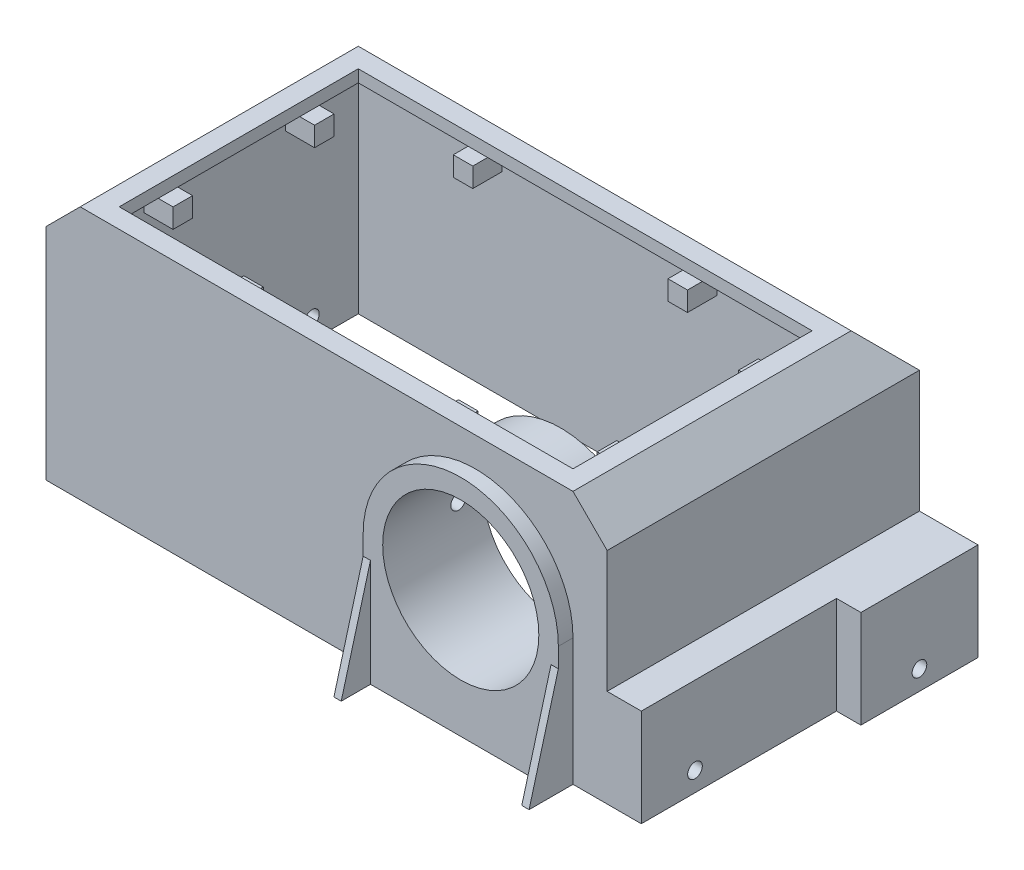
SolidWorks part; units mm, degrees
ref_plane "Front" through (0, 0, 0) normal (0, 0, 1) x (1, 0, 0)
ref_plane "Top" through (0, 0, 0) normal (0, 1, 0) x (1, 0, 0)
ref_plane "Right" through (0, 0, 0) normal (1, 0, 0) x (0, 0, -1)
sketch "Sketch1" plane through (0, 0, 0) normal (0, 0, 1) x (1, 0, 0)
  line L0 (63.5, -6) -> (51.5, -6)
  line L1 (-63.5, -26) -> (63.5, -26)
  line L2 (-63.5, -26) -> (-63.5, 26)
  line L3 (-63.5, 26) -> (63.5, 26)
  line L4 (63.5, -26) -> (63.5, 26)
  line L5 (-63.5, -26) -> (63.5, 26) construction
  line L6 (-63.5, 26) -> (63.5, -26) construction
  line L7 (51.5, -6) -> (51.5, 26)
  point P0 (0, 0)
  dimension "D1" = 52
  dimension "D2" = 127
  dimension "D3" = 12
  dimension "D4" = 20
extrude "Boss-Extrude1" add sketch "Sketch1" along normal blind 64 contours L0 L7 L3 L2 L1 L4 region at (-3.5498, -0.6174, 0)
sketch "Sketch2" plane through (0, 0, 64) normal (0, 0, 1) x (1, 0, 0)
  line L0 (-63.5, -26) -> (63.5, -26) construction
  line L1 (51.5, -6) -> (51.5, 26) construction
  circle A0 centre (24.5, 0) radius 16
  circle A1 centre (24.5, 0) radius 20
  dimension "D1" = 32
  dimension "D3" = 26
  dimension "D4" = 27
  dimension "D2" = 4
extrude "Boss-Extrude2" add sketch "Sketch2" along normal blind 3
chamfer "Chamfer1" distance 7 angle 45 3 edges at (-63.5, 26, 32) (-6, 26, 0) (51.5, 26, 32)
sketch "Sketch3" plane through (0, 0, 67) normal (0, 0, 1) x (1, 0, 0)
  line L0 (4.5, 0) -> (4.5, -26)
  line L1 (-63.5, -26) -> (63.5, -26) construction
  line L2 (6.5, -8.7178) -> (6.5, -26)
  line L3 (44.5, 0) -> (44.5, -26)
  line L4 (42.5, -8.7178) -> (42.5, -26)
  line L5 (6.5, 0) -> (6.5, -26) construction
  line L6 (42.5, 0) -> (42.5, -26) construction
  line L7 (4.5, 0) -> (4.5, -26) construction
  line L8 (4.5, -26) -> (44.5, -26)
  circle A0 centre (24.5, 0) radius 20 construction
  circle A1 centre (24.5, 0) radius 20 construction
  circle A2 centre (24.5, 0) radius 20
  circle M3 centre (24.5, 0) radius 20
  dimension "D1" = 2
  dimension "D2" = 2
extrude "Boss-Extrude3" add sketch "Sketch3" against normal up to next contours L0 L8 L2 M3 | L4 L8 L3 M3 | L2 L8 L4 M3 region at (5.4427, -15.8325, 67) region at (43.5573, -15.8325, 67) region at (24.5, -20.8713, 67)
sketch "Sketch4" plane through (0, 0, 67) normal (0, 0, 1) x (1, 0, 0)
  line L1 (4.5, -26) -> (6, -26)
  line L2 (4.5, -26) -> (4.5, -4)
  line L3 (4.5, -4) -> (6, -4)
  line L4 (6, -26) -> (6, -4)
  line L5 (4.5, -26) -> (6, -4) construction
  line L6 (4.5, -4) -> (6, -26) construction
  line L7 (44.5, -26) -> (43, -26)
  line L8 (44.5, -26) -> (44.5, -4)
  line L9 (44.5, -4) -> (43, -4)
  line L10 (43, -26) -> (43, -4)
  line L11 (44.5, -26) -> (43, -4) construction
  line L12 (44.5, -4) -> (43, -26) construction
  circle A0 centre (24.5, 0) radius 16 construction
  circle A1 centre (24.5, 0) radius 16
  point P7 (5.25, -15)
  point P13 (43.75, -15)
  line M2 (4.5, 0) -> (4.5, -26)
  line M3 (4.5, -26) -> (44.5, -26)
  line M4 (44.5, -26) -> (44.5, 0)
  dimension "D1" = 22
  dimension "D2" = 1.5
  dimension "D3" = 22
  dimension "D4" = 1.5
extrude "Boss-Extrude4" add sketch "Sketch4" along normal blind 6 contours L10 L9 M3 M4 | L4 L3 M3 M2 region at (5.25, -15, 67) region at (43.75, -15, 67)
sketch "Sketch5" plane through (4.5, 0, 0) normal (-1, 0, 0) x (0, 0, 1)
  line L0 (67, -4) -> (73, -26)
  line L1 (73, -26) -> (73, -4)
  line L2 (73, -4) -> (67, -4)
extrude "Cut-Extrude1" cut sketch "Sketch5" against normal through all
sketch "Sketch6" plane through (0, -6, 0) normal (0, 1, 0) x (1, 0, 0)
  line L1 (63.5, -64) -> (58.5, -64)
  line L2 (63.5, -64) -> (63.5, -24)
  line L3 (63.5, -24) -> (58.5, -24)
  line L4 (58.5, -64) -> (58.5, -24)
  line L5 (63.5, -64) -> (58.5, -24) construction
  line L6 (63.5, -24) -> (58.5, -64) construction
  point P4 (61, -44)
  dimension "D1" = 40
  dimension "D2" = 5
extrude "Cut-Extrude2" cut sketch "Sketch6" against normal through all
shell "Shell1" thickness 2.5 removed face at (22.3571, -26, 52.1429)
sketch "Sketch7" plane through (0, 0, 64) normal (0, 0, 1) x (1, 0, 0)
  circle A1 centre (24.5, 0) radius 16
  circle A2 centre (24.5, 0) radius 16
  dimension "D1" = 0
extrude "Cut-Extrude3" cut sketch "Sketch7" against normal up to next
sketch "Sketch8" plane through (0, 0, 61.5) normal (0, 0, -1) x (-1, 0, 0)
  circle A0 centre (-24.5, 0) radius 16 construction
  circle A1 centre (-24.5, 0) radius 16
  arc A2 (-42, -6) -> (-7, -6) centre (-24.5, 0) ccw construction
  arc A3 (-42, -6) -> (-7, -6) centre (-24.5, 0) ccw
  circle A4 centre (-24.5, 0) radius 18.5
  circle M2 centre (-24.5, 0) radius 16
  arc M14 (-42, -6) -> (-7, -6) centre (-24.5, 0) ccw
extrude "Boss-Extrude5" add sketch "Sketch8" along normal blind 15 contours A4 M14 M2 region at (27.4554, 17.7321, 61.5)
sketch "Sketch9" plane through (0, 26, 0) normal (0, 1, 0) x (1, 0, 0)
  line L14 (40.5, -60) -> (40.5, -11)
  line L15 (-52.5, -60) -> (40.5, -60)
  line L16 (-52.5, -11) -> (-52.5, -60)
  line L17 (40.5, -11) -> (-52.5, -11)
  line L18 (40.5, -60) -> (40.5, -11)
  line L19 (-52.5, -60) -> (40.5, -60)
  line L20 (-52.5, -11) -> (-52.5, -60)
  line L21 (40.5, -11) -> (-52.5, -11)
  dimension "D1" = 4
extrude "Cut-Extrude4" cut sketch "Sketch9" against normal up to next
sketch "Sketch10" plane through (0, 23.5, 0) normal (0, -1, 0) x (1, 0, 0)
  line L0 (-55.4645, 8.0355) -> (-55.4645, 61.5) construction
  line L1 (-55.4645, 52) -> (-49.4645, 52)
  line L2 (-55.4645, 52) -> (-55.4645, 48)
  line L3 (-55.4645, 48) -> (-49.4645, 48)
  line L4 (-49.4645, 52) -> (-49.4645, 48)
  line L5 (-55.4645, 52) -> (-49.4645, 48) construction
  line L6 (-55.4645, 48) -> (-49.4645, 52) construction
  line L7 (40.5, 60) -> (-52.5, 60) construction
  line L8 (-55.4645, 23) -> (-49.4645, 23)
  line L9 (-55.4645, 23) -> (-55.4645, 19)
  line L10 (-55.4645, 19) -> (-49.4645, 19)
  line L11 (-49.4645, 23) -> (-49.4645, 19)
  line L12 (-55.4645, 23) -> (-49.4645, 19) construction
  line L13 (-55.4645, 19) -> (-49.4645, 23) construction
  line L14 (-52.5, 11) -> (40.5, 11) construction
  line L15 (-6, 11) -> (-6, 19.8293) construction
  line L16 (43.4645, 19) -> (37.4645, 23) construction
  line L17 (43.4645, 23) -> (37.4645, 19) construction
  line L18 (43.4645, 48) -> (37.4645, 52) construction
  line L19 (43.4645, 52) -> (37.4645, 48) construction
  line L20 (37.4645, 23) -> (37.4645, 19)
  line L21 (43.4645, 19) -> (37.4645, 19)
  line L22 (43.4645, 23) -> (43.4645, 19)
  line L23 (43.4645, 23) -> (37.4645, 23)
  line L24 (37.4645, 52) -> (37.4645, 48)
  line L25 (43.4645, 48) -> (37.4645, 48)
  line L26 (43.4645, 52) -> (43.4645, 48)
  line L27 (43.4645, 52) -> (37.4645, 52)
  line L28 (43.4645, 8.0355) -> (-55.4645, 8.0355) construction
  line L29 (-30, 8.0355) -> (-26, 8.0355)
  line L30 (-30, 8.0355) -> (-30, 14.0355)
  line L31 (-30, 14.0355) -> (-26, 14.0355)
  line L32 (-26, 8.0355) -> (-26, 14.0355)
  line L33 (-30, 8.0355) -> (-26, 14.0355) construction
  line L34 (-30, 14.0355) -> (-26, 8.0355) construction
  line L35 (40.5, 35.5) -> (33.5247, 35.5) construction
  line L36 (14, 8.0355) -> (18, 8.0355)
  line L37 (14, 8.0355) -> (14, 14.0355)
  line L38 (14, 14.0355) -> (18, 14.0355)
  line L39 (18, 8.0355) -> (18, 14.0355)
  line L40 (14, 8.0355) -> (18, 14.0355) construction
  line L41 (14, 14.0355) -> (18, 8.0355) construction
  line L42 (40.5, 11) -> (40.5, 60) construction
  line L43 (14, 56.9645) -> (18, 62.9645) construction
  line L44 (14, 62.9645) -> (18, 56.9645) construction
  line L45 (-30, 56.9645) -> (-26, 62.9645) construction
  line L46 (-30, 62.9645) -> (-26, 56.9645) construction
  line L47 (-6, 60) -> (-6, 51.1707) construction
  line L48 (18, 62.9645) -> (18, 56.9645)
  line L49 (14, 56.9645) -> (18, 56.9645)
  line L50 (14, 62.9645) -> (14, 56.9645)
  line L51 (14, 62.9645) -> (18, 62.9645)
  line L52 (-26, 62.9645) -> (-26, 56.9645)
  line L53 (-30, 56.9645) -> (-26, 56.9645)
  line L54 (-30, 62.9645) -> (-30, 56.9645)
  line L55 (-30, 62.9645) -> (-26, 62.9645)
  point P4 (-52.4645, 50)
  point P11 (-52.4645, 21)
  point P26 (40.4645, 21)
  point P27 (40.4645, 50)
  point P32 (-28, 11.0355)
  point P39 (16, 11.0355)
  point P54 (16, 59.9645)
  point P55 (-28, 59.9645)
  dimension "D1" = 4
  dimension "D2" = 6
  dimension "D3" = 4
  dimension "D4" = 6
  dimension "D5" = 8
  dimension "D6" = 8
  dimension "D7" = 6
  dimension "D8" = 4
  dimension "D9" = 6
  dimension "D10" = 4
  dimension "D11" = 20
  dimension "D12" = 20
extrude "Boss-Extrude6" add sketch "Sketch10" along normal blind 4
sketch "Sketch11" plane through (-63.5, 0, 0) normal (-1, 0, 0) x (0, 0, 1)
  line L0 (0, -26) -> (0, 19) construction
  line L1 (64, -26) -> (64, 19) construction
  line L2 (0, -26) -> (26.355, -26) construction
  circle A0 centre (53, -22) radius 1.5
  circle A1 centre (12, -22) radius 1.5
  point P10 (0, 0)
  dimension "D1" = 3
  dimension "D2" = 3
  dimension "D3" = 12
  dimension "D4" = 11
  dimension "D5" = 4
extrude "Cut-Extrude5" cut sketch "Sketch11" against normal through all
sketch "Sketch12" plane through (0, 0, 0) normal (1, 0, 0) x (0, 0, -1)
  line L0 (-46.5, 0) -> (-51.5, 0) construction
  line L1 (-46.5, -18.5) -> (-46.5, 18.5) construction
  circle A0 centre (-51.5, 0) radius 1.55
  dimension "D2" = 3.1
  dimension "D1" = 5
extrude "Cut-Extrude6" cut sketch "Sketch12" along normal blind 44
